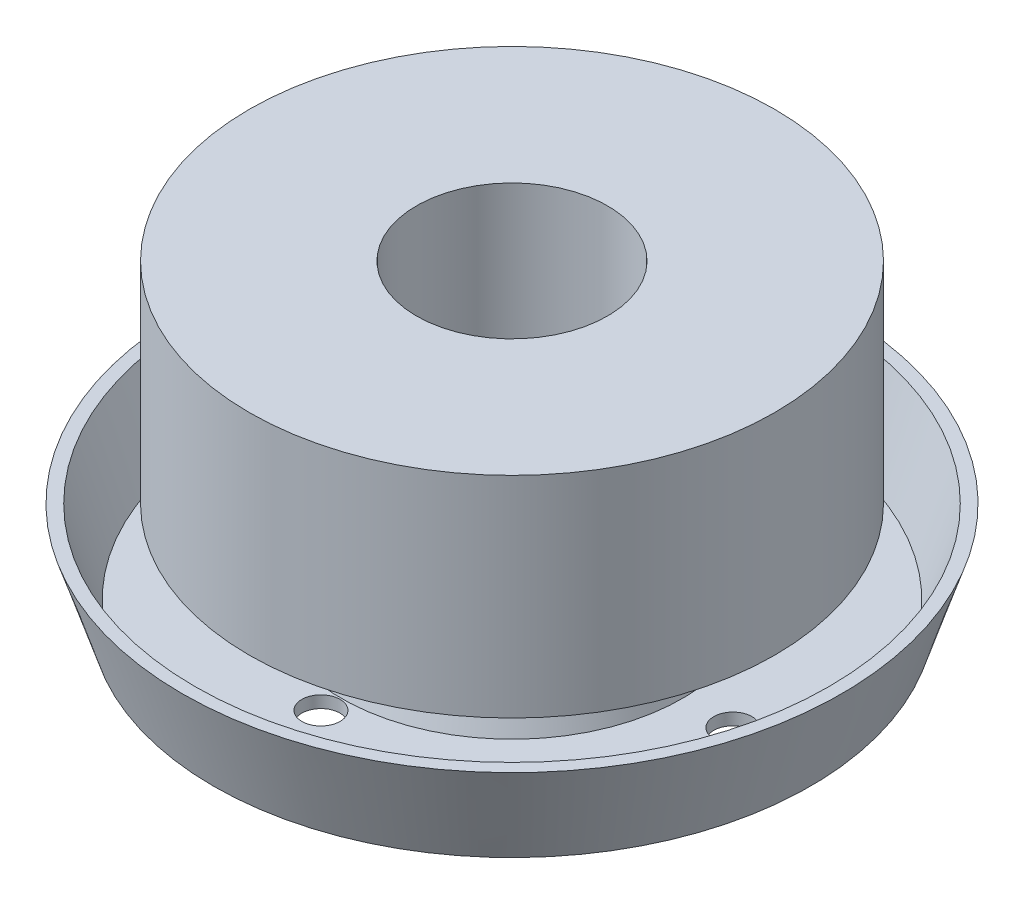
SolidWorks part; units mm, degrees
ref_plane "Front Plane" through (0, 0, 0) normal (0, 0, 1) x (1, 0, 0)
ref_plane "Top Plane" through (0, 0, 0) normal (0, 1, 0) x (1, 0, 0)
ref_plane "Right Plane" through (0, 0, 0) normal (1, 0, 0) x (0, 0, -1)
sketch "Sketch1" plane through (0, 0, 0) normal (0, 0, 1) x (1, 0, 0)
  line L0 (0, 0) -> (0, 12.8) construction
  line L1 (1.5, 4) -> (1.5, 0)
  line L2 (1.5, 0) -> (12.5, 0)
  line L3 (12.5, 0) -> (13.8, 4)
  line L4 (1.5, 4) -> (6, 4)
  line L5 (6, 4) -> (7.1375, 0.5)
  line L6 (7.1375, 0.5) -> (12.1368, 0.5)
  line L7 (12.1368, 0.5) -> (13.2743, 4)
  line L8 (13.2743, 4) -> (13.8, 4)
  line L9 (9.6371, 0.5) -> (9.6371, 0) construction
  line L10 (12.7055, 2.25) -> (13.181, 2.0955) construction
  dimension "D1" = 3
  dimension "D2" = 12.8
  dimension "D3" = 27.6
  dimension "D4" = 25
  dimension "D5" = 4
  dimension "D6" = 0.5
  dimension "D7" = 12
revolve "Revolve1" add sketch "Sketch1" angle 360 about L0
sketch "Sketch2" plane through (0, 4, 0) normal (0, 1, 0) x (1, 0, 0)
  circle A0 centre (0, 0) radius 11
  circle A1 centre (0, 0) radius 4
  dimension "D1" = 22
  dimension "D2" = 8
extrude "Boss-Extrude1" add sketch "Sketch2" along normal blind 8.8
hole_wizard "M2x0.4 Tapped Hole1" positions "Sketch4" profile "Sketch3" tap size "M2x0.4" standard "ANSI Metric" end condition up to next
sketch "Sketch4" plane through (0, 0, 0) normal (0, -1, 0) x (-1, 0, 0)
  line L0 (0, 8) -> (0, -8) construction
  line L1 (-9.25, 0) -> (9.25, 0) construction
  point P0 (0, 8)
  point P2 (0, -8)
  point P10 (-9.25, 0)
  point P12 (9.25, 0)
  dimension "D1" = 18.5
  dimension "D2" = 16
sketch "Sketch3" plane through (0, 0, -8) normal (1, 0, 0) x (0, 0, -1)
  line L0 (0, 0) -> (0, 0.5)
  line L1 (0, 0.5) -> (0.8, 0.5)
  line L2 (0.8, 0.5) -> (0.8, 0)
  line L5 (0.8, 0) -> (0, 0)
  line L11 (0, -6.35) -> (0, 107.95) construction
  dimension "Thread Major Dia." = 1.6
  dimension "Thru Tap Drill Depth" = 0.5
sketch "Sketch5" plane through (0, 0, 0) normal (0, -1, 0) x (1, 0, 0)
  line L0 (0, 0) -> (-8.8388, -8.8388) construction
  line L1 (0, -8) -> (0, 8) construction
  line L2 (9.25, 0) -> (-9.25, 0) construction
  line L3 (8.8388, -8.8388) -> (-8.8388, 8.8388) construction
  circle A0 centre (0, 0) radius 12.5 construction
  circle A1 centre (0, -8) radius 0.8 construction
  circle A2 centre (-9.25, 0) radius 0.8 construction
  dimension "D1" = 45
ref_plane "Plane1" through (0, 0, 0) normal (-0.7071, 0, -0.7071) x (-0.7071, 0, 0.7071)
sketch "Sketch6" plane through (0, 0, 0) normal (-0.7071, 0, -0.7071) x (-0.7071, 0, 0.7071)
  line L0 (13.8, 4) -> (-13.8, 4) construction
  line L1 (-1.25, 2.75) -> (1.25, 2.75) construction
  line L2 (-1.25, 3.475) -> (1.25, 3.475)
  line L3 (-1.25, 2.025) -> (1.25, 2.025)
  circle A0 centre (0, 2.75) radius 0.625 construction
  circle A1 centre (1.25, 2.75) radius 0.625 construction
  circle A2 centre (-1.25, 2.75) radius 0.625 construction
  arc A3 (-1.25, 3.475) -> (-1.25, 2.025) centre (-1.25, 2.75) ccw
  arc A4 (1.25, 2.025) -> (1.25, 3.475) centre (1.25, 2.75) ccw
  point P6 (-0.625, 2.75)
  point P8 (0.625, 2.75)
  point P11 (0, 2.75)
  dimension "D1" = 1.25
  dimension "D3" = 0.1
  dimension "D2" = 1.25
extrude "Boss-Extrude3" add sketch "Sketch6" along normal blind 5 and the other way up to next from offset 14
